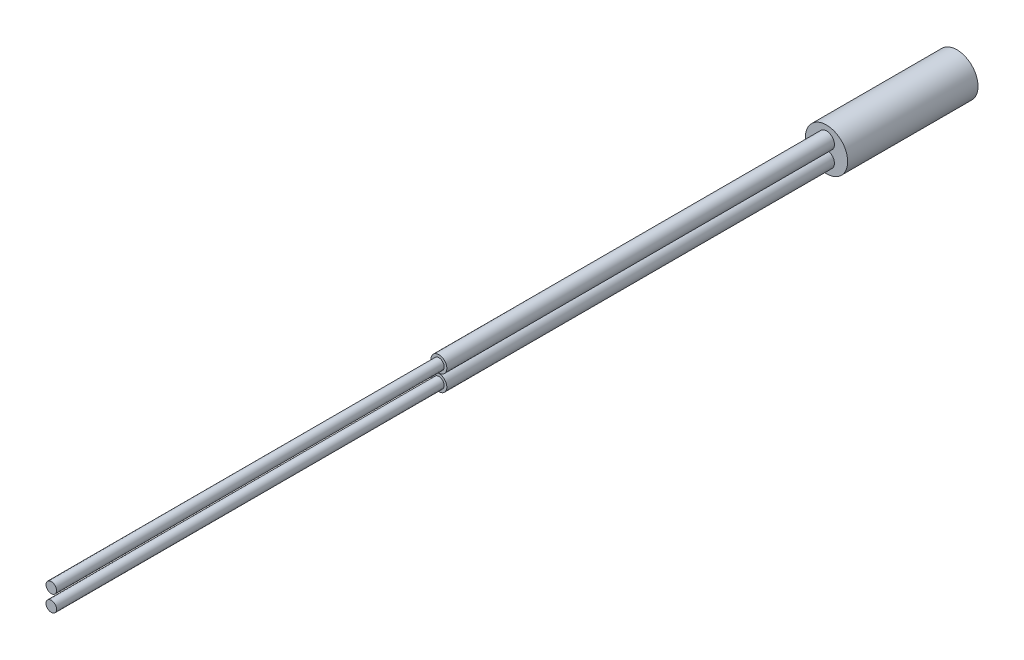
SolidWorks part; units mm, degrees
material "acero"
ref_plane "Alzado" through (0, 0, 0) normal (0, 0, 1) x (1, 0, 0)
ref_plane "Planta" through (0, 0, 0) normal (0, 1, 0) x (1, 0, 0)
ref_plane "Vista lateral" through (0, 0, 0) normal (1, 0, 0) x (0, 0, -1)
sketch "Croquis1" plane through (0, 0, 0) normal (0, 0, 1) x (1, 0, 0)
  circle A0 centre (0, 0) radius 3
  dimension "D1" = 6
extrude "Saliente-Extruir1" add sketch "Croquis1" along normal blind 18
ref_plane "Plano1" through (0, 0.5, 0) normal (0, -1, 0) x (-1, 0, 0)
ref_plane "Plano2" through (0, -9.5, 0) normal (0, -1, 0) x (-1, 0, 0)
ref_plane "Plano3" through (-23.0763, 0, 10.7606) normal (-0.9063, 0, 0.4226) x (0.4226, 0, 0.9063)
sketch3d "Croquis3D1"
  line L0 (0, 0, 18) -> (0, 0, 21)
  line L1 (0, 0, 18) -> (0, 0, 0) construction
  line L2 (-17.166, -4.6752, 23.4353) -> (-17.166, -8.5854, 23.4353)
  line L3 (-6.75, -14.9111, 10) -> (-6.75, 16.5741, 10) construction
  spline S0 degree 3 poles (0, 0, 21) (0, 0, 27.5004) (-12.019, 3.2907, 25.754) (-17.166, -2.2029, 23.4353) (-17.166, -4.6752, 23.4353) knots 0 0 0 0 0.663423 1 1 1 1
  dimension "D1" = 17
  dimension "D2" = 3
sketch "Croquis2" plane through (0, 0, 18) normal (0, 0, 1) x (1, 0, 0)
  circle A0 centre (0, 0) radius 0.8 construction
  circle A1 centre (-0.8, 0) radius 0.75
  circle A2 centre (0.8, 0) radius 0.75
  dimension "D1" = 1.6
  dimension "D2" = 1.5
sweep "Barrer1" [suppressed] add profiles "Croquis2" path "Croquis3D1"
extrude "Saliente-Extruir2" add sketch "Croquis1<2>" along normal blind 21.5 and the other way blind 1.5
sketch "Croquis1<2>" plane through (0, 0, 0) normal (0, 0, 1) x (1, 0, 0) same geometry as "Croquis1"
sketch "Croquis3" plane through (0, 0, -1.5) normal (0, 0, -1) x (-1, 0, 0)
  circle A0 centre (0, 0) radius 3
  dimension "D1" = 6
extrude "Cortar-Extruir1" cut sketch "Croquis3" against normal blind 4.5
sketch "Croquis4" plane through (0, 0, 0) normal (1, 0, 0) x (0, 0, -1)
  line L0 (-18.6464, 0) -> (-3, 0) construction
  line L1 (-3, -3) -> (-3, 3) construction
  line L2 (-3, 0) -> (7.8098, 15.8525) construction
  dimension "D1" = 34.29
sketch3d "Croquis3D4"
  line L0 (0, 0, 3) -> (-18.9322, 0, 3) construction
ref_plane "Plano4" through (0, 1.3964, 2.0478) normal (0, -0.5634, -0.8262) x (-1, 0, 0)
sketch3d "Croquis3D3" [suppressed]
  line L0 (-1.9716, 13.6377, 26.3138) -> (-2.2072, 8.1317, 30.0679)
  line L1 (-5.6206, 5.0135, 32.2682) -> (-41.5, -3.146, 34.1262)
  line L2 (-47.8249, -2.5398, 38.3697) -> (-47.8249, -22.8208, 52.1977)
  line L3 (-43.8249, -26.1257, 54.4511) -> (-27.8372, -26.1257, 54.4511)
  line L4 (-41, -0.2448, 33.0559) -> (-27.23, 0.0992, 33.3873)
  line L5 (-27.23, 0.0992, 33.3873) -> (-27.23, 3.5226, 33.3873)
  line L6 (-27.23, 3.5226, 33.3873) -> (-1.9922, 3.5226, 33.3873)
ref_plane "Plano5" through (0, 17.1711, 25.1813) normal (0, -0.5634, -0.8262) x (-1, 0, 0)
sketch "Croquis6" plane through (0, 17.1711, 25.1813) normal (0, -0.5634, -0.8262) x (-1, 0, 0)
  line L0 (0, -15.6127) -> (0, -12.1127) construction
  line L1 (22, -19.1127) -> (22, -15.6127)
  line L4 (22, -15.6127) -> (0, -15.6127)
  line L5 (47.5, -19.1127) -> (22, -19.1127)
  line L6 (47.5, -19.1127) -> (47.5, -50.6127)
  line L7 (47.5, -50.6127) -> (33.5, -50.6127)
  ellipse E0 centre (0, -12.1127) end of major axis (-3, -12.1127) minor radius 2.4786 construction
  dimension "D1" = 38.5
  dimension "D2" = 47.5
  dimension "D3" = 7
  dimension "D4" = 3.5
  dimension "D5" = 22
  dimension "D6" = 14
sketch3d "Croquis3D5"
  line L0 (0, 0, 21.5) -> (0, 4.2719, 33.9772) construction
  line L1 (0, 0, 21.5) -> (0, 0, 3) construction
  line L2 (-22, 3.4328, 34.5494) -> (-21.2499, 4.2719, 33.9772) construction
  line L3 (-47.5, -24.645, 53.6956) -> (-33.5, -24.645, 53.6956) construction
  line L4 (-47.5, 1.3802, 35.9491) -> (-47.5, -24.645, 53.6956) construction
  line L5 (-44.5, -24.645, 53.6956) -> (-47.5, -22.1664, 52.0054) construction
  line L6 (-46.4718, -0.0371, 36.9155) -> (-45.5, 1.3802, 35.9491) construction
  line L7 (-47.5, 1.3802, 35.9491) -> (-22, 1.3802, 35.9491) construction
  line L8 (-22, 1.3802, 35.9491) -> (-22, 4.2719, 33.9772) construction
  line L9 (-22.8792, 1.3802, 35.9491) -> (-22, 2.1057, 35.4543) construction
  line L10 (-22, 4.2719, 33.9772) -> (0, 4.2719, 33.9772) construction
  line L11 (-2, 4.2719, 33.9772) -> (0, 3.6241, 32.0851) construction
  arc A0 (-42.3787, -24.645, 53.6956) -> (-47.5, -20.4137, 50.8103) centre (-42.3787, -20.4137, 50.8103) cw
  arc A1 (-47.5, -1.9109, 38.1933) -> (-43.5165, 1.3802, 35.9491) centre (-43.5165, -1.9109, 38.1933) cw
  arc A2 (-23.5, 1.3802, 35.9491) -> (-22, 2.6195, 35.104) centre (-23.5, 2.6195, 35.104) cw
  arc A4 (-3.4142, 4.2719, 33.9772) -> (0, 3.166, 30.7471) centre (-3.4142, 3.166, 30.7471) cw
  arc A5 (-22, 3.0326, 34.8223) -> (-20.5, 4.2719, 33.9772) centre (-20.5, 3.0326, 34.8223) cw
  point P7 (-42.3787, -23.299, 46.5791)
  point P16 (-46, -23.4057, 52.8505)
  point P25 (-43.5165, -4.1551, 34.9021)
  point P27 (-45.9859, 0.6716, 36.4323)
  point P29 (-23.5, 3.4646, 36.3433)
  point P31 (-22.4396, 1.743, 35.7017)
  point P44 (-20.5, 2.1875, 33.583)
  point P46 (-21.625, 3.8524, 34.2633)
  point P51 (-3.4142, 6.3961, 29.6412)
  point P53 (-1, 3.948, 33.0311)
  dimension "D5" = 1.5
  dimension "D2" = 3
  dimension "D11" = 3
  dimension "D3" = 2
  dimension "D4" = 2
  dimension "D7" = 1.5
  dimension "D9" = 2
  dimension "D10" = 2
sketch3d "Croquis3D7"
  line L0 (-47.5, -24.645, 53.6956) -> (-33.5, -24.645, 53.6956) construction
  line L1 (-47.5, 1.3802, 35.9491) -> (-47.5, -24.645, 53.6956) construction
  line L2 (-47.5, 1.3802, 35.9491) -> (-22, 1.3802, 35.9491) construction
  line L3 (-22, 1.3802, 35.9491) -> (-22, 4.2719, 33.9772) construction
  line L4 (-22, 4.2719, 33.9772) -> (0, 4.2719, 33.9772) construction
  line L5 (0, 0, 21.5) -> (0, 4.2719, 33.9772) construction
  line L6 (-42.3787, -24.645, 53.6956) -> (-33.5, -24.645, 53.6956)
  line L7 (-47.5, -1.9109, 38.1933) -> (-47.5, -20.4137, 50.8103)
  line L8 (-43.5165, 1.3802, 35.9491) -> (-23.5, 1.3802, 35.9491)
  line L9 (-22, 2.6195, 35.104) -> (-22, 3.0326, 34.8223)
  line L10 (-20.5, 4.2719, 33.9772) -> (-3.4142, 4.2719, 33.9772)
  line L11 (0, 0, 21.5) -> (0, 3.166, 30.7471)
  arc A0 (-42.3787, -24.645, 53.6956) -> (-47.5, -20.4137, 50.8103) centre (-42.3787, -20.4137, 50.8103) ccw construction
  arc A1 (-47.5, -1.9109, 38.1933) -> (-43.5165, 1.3802, 35.9491) centre (-43.5165, -1.9109, 38.1933) ccw construction
  arc A2 (-23.5, 1.3802, 35.9491) -> (-22, 2.6195, 35.104) centre (-23.5, 2.6195, 35.104) ccw construction
  arc A4 (-3.4142, 4.2719, 33.9772) -> (0, 3.166, 30.7471) centre (-3.4142, 3.166, 30.7471) ccw construction
  arc A5 (-42.3787, -24.645, 53.6956) -> (-47.5, -20.4137, 50.8103) centre (-42.3787, -20.4137, 50.8103) ccw
  arc A6 (-47.5, -1.9109, 38.1933) -> (-43.5165, 1.3802, 35.9491) centre (-43.5165, -1.9109, 38.1933) ccw
  arc A7 (-23.5, 1.3802, 35.9491) -> (-22, 2.6195, 35.104) centre (-23.5, 2.6195, 35.104) ccw
  arc A8 (-22, 3.0326, 34.8223) -> (-20.5, 4.2719, 33.9772) centre (-20.5, 3.0326, 34.8223) ccw construction
  arc A9 (-3.4142, 4.2719, 33.9772) -> (0, 3.166, 30.7471) centre (-3.4142, 3.166, 30.7471) ccw
  arc A10 (-22, 3.0326, 34.8223) -> (-20.5, 4.2719, 33.9772) centre (-20.5, 3.0326, 34.8223) ccw
  point P5 (-42.3787, -23.299, 46.5791)
  point P10 (-43.5165, -4.1551, 34.9021)
  point P15 (-23.5, 3.4646, 36.3433)
  point P20 (-20.5, 2.1875, 33.583)
  point P25 (-3.4142, 6.3961, 29.6412)
  point P27 (-42.3787, -23.299, 46.5791)
  point P28 (-43.5165, -4.1551, 34.9021)
  point P29 (-23.5, 3.4646, 36.3433)
  point P31 (-3.4142, 6.3961, 29.6412)
  point P32 (-20.5, 2.1875, 33.583)
ref_plane "Plano6" through (-33.5, -24.645, 53.6956) normal (1, 0, 0) x (0, 0, -1)
sketch "Croquis7" plane through (-33.5, -24.645, 53.6956) normal (1, 0, 0) x (0, 0, -1)
  line L0 (0.9708, -0.662) -> (-0.9708, 0.662) construction
  line L1 (17.7465, 26.0252) -> (0, 0) construction
  circle A0 centre (-0.9708, 0.662) radius 1.125
  circle A1 centre (0.9708, -0.662) radius 1.125
  dimension "D1" = 2.25
  dimension "D2" = 0.1
  dimension "D3" = 4.6
sweep "Barrer2" [suppressed] add profiles "Croquis7" path "Croquis3D7"
sketch "Croquis8" [suppressed] plane through (-33.5, 0, 0) normal (1, 0, 0) x (0, 0, -1)
  circle A0 centre (-54.6664, -23.983) radius 0.75
  circle A1 centre (-52.7248, -25.3069) radius 0.75
  dimension "D1" = 1.5
sketch3d "Croquis3D8" [suppressed]
  line L0 (-33.5, -25.3069, 52.7248) -> (-32.5, -25.3069, 52.7248)
  line L1 (-31.5, -25.8805, 51.9057) -> (-31.5, -26.6156, 50.8559) construction
  line L2 (-31.5, -25.3069, 52.7248) -> (-31.5, -25.3069, 45.2282) construction
  arc A0 (-32.5, -25.3069, 52.7248) -> (-31.5, -25.8805, 51.9057) centre (-32.5, -25.8805, 51.9057) ccw
  point P7 (-31.5, -25.3069, 52.7248)
  point P9 (-32.5, -25.0614, 51.3321)
  dimension "D3" = 1
  dimension "D1" = 2
  dimension "D2" = 1
  dimension "D5" = 1
  dimension "D4" = 35
sweep "Barrer3" [suppressed] add profiles "Croquis8" path "Croquis3D8"
sketch "Croquis9" plane through (0, 0, 21.5) normal (0, 0, 1) x (1, 0, 0)
  line L0 (0, 1.15) -> (0, -1.15) construction
  circle A0 centre (0, -1.15) radius 1.125
  circle A1 centre (0, 1.15) radius 1.125
  dimension "D1" = 2.25
  dimension "D2" = 2.3
extrude "Saliente-Extruir3" add sketch "Croquis9" along normal blind 55
sketch "Croquis10" plane through (0, 0, 21.5) normal (0, 0, 1) x (1, 0, 0)
  circle A0 centre (0, -1.15) radius 0.75
  circle A1 centre (0, 1.15) radius 0.75
  circle A2 centre (0, 1.15) radius 1.125 construction
  circle A3 centre (0, -1.15) radius 1.125 construction
  dimension "D1" = 1.5
extrude "Saliente-Extruir4" add sketch "Croquis10" along normal blind 110
